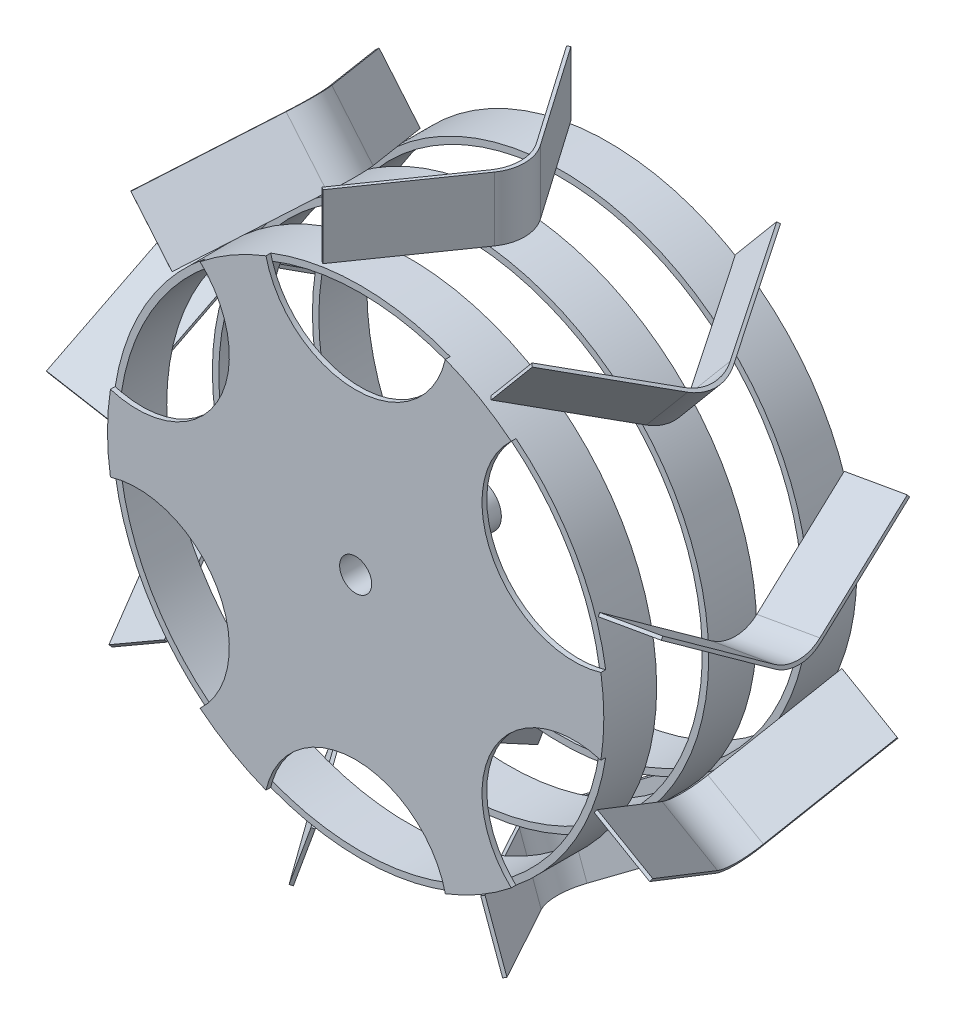
SolidWorks part; units mm, degrees
other "Папка сварных швов"
ref_plane "Спереди" through (0, 0, 0) normal (0, 0, 1) x (1, 0, 0)
ref_plane "Сверху" through (0, 0, 0) normal (0, 1, 0) x (1, 0, 0)
ref_plane "Справа" through (0, 0, 0) normal (1, 0, 0) x (0, 0, -1)
sketch "Эскиз1" plane through (0, 0, 0) normal (0, 0, 1) x (1, 0, 0)
  arc A0 (-56.0167, 144.5238) -> (-97.153, 120.7738) centre (0, 0) ccw
  arc A1 (-56.0167, 144.5238) -> (56.0167, 144.5238) centre (0, 157.5) ccw
  arc A2 (97.153, 120.7738) -> (153.1696, 23.75) centre (136.399, 78.75) ccw
  arc A3 (153.1696, -23.75) -> (97.153, -120.7738) centre (136.399, -78.75) ccw
  arc A4 (56.0167, -144.5238) -> (-56.0167, -144.5238) centre (0, -157.5) ccw
  arc A5 (-97.153, -120.7738) -> (-153.1696, -23.75) centre (-136.399, -78.75) ccw
  arc A6 (-153.1696, 23.75) -> (-97.153, 120.7738) centre (-136.399, 78.75) ccw
  arc A7 (97.153, 120.7738) -> (56.0167, 144.5238) centre (0, 0) ccw
  arc A8 (-153.1696, 23.75) -> (-153.1696, -23.75) centre (0, 0) ccw
  arc A9 (-97.153, -120.7738) -> (-56.0167, -144.5238) centre (0, 0) ccw
  arc A10 (56.0167, -144.5238) -> (97.153, -120.7738) centre (0, 0) ccw
  arc A11 (153.1696, -23.75) -> (153.1696, 23.75) centre (0, 0) ccw
  point P23 (0, 0)
  dimension "D1" = 310
  dimension "D2" = 115
  dimension "D3" = 100
  dimension "D4" = 6
extrude "Бобышка-Вытянуть1" add sketch "Эскиз1" against normal blind 3
sketch "Эскиз2" plane through (0, 0, -3) normal (0, 0, -1) x (-1, 0, 0)
  circle A0 centre (0, 0) radius 14
  circle A1 centre (0, 0) radius 10
  dimension "D1" = 28
  dimension "D2" = 20
extrude "Вырез-Вытянуть1" cut sketch "Эскиз2" against normal blind 3 contours A0
extrude "Бобышка-Вытянуть2" add sketch "Эскиз2<4>" along normal blind 74 and the other way blind 3
sketch "Эскиз2<4>" plane through (0, 0, -3) normal (0, 0, -1) x (-1, 0, 0) same geometry as "Эскиз2"
sketch "Эскиз4" plane through (0, 0, 0) normal (0, 1, 0) x (1, 0, 0)
  line L0 (14, 77) -> (-14, 77) construction
  circle A0 centre (0, 56.5) radius 4
  dimension "D1" = 8
  dimension "D2" = 16.5
extrude "Вырез-Вытянуть2" cut sketch "Эскиз4" against normal up to next and the other way up to next
sketch "Эскиз5" plane through (0, 0, -3) normal (0, 0, -1) x (-1, 0, 0)
  circle A0 centre (0, 0) radius 155
  circle A1 centre (0, 0) radius 151
  dimension "D1" = 310
  dimension "D2" = 4
extrude "Бобышка-Вытянуть3" add sketch "Эскиз5" along normal blind 30
ref_plane "Плоскость1" through (0, 0, -80.5) normal (0, 0, -1) x (-1, 0, 0)
ref_plane "Плоскость2" through (0, 0, -128) normal (0, 0, -1) x (-1, 0, 0)
sketch "Эскиз6" plane through (0, 0, -128) normal (0, 0, -1) x (-1, 0, 0)
  circle A0 centre (0, 0) radius 155
  circle A1 centre (0, 0) radius 151
  dimension "D1" = 310
  dimension "D2" = 4
sketch "Эскиз7" plane through (0, 0, -80.5) normal (0, 0, -1) x (-1, 0, 0)
  circle A0 centre (0, 0) radius 155
  circle A1 centre (0, 0) radius 151
  dimension "D1" = 310
  dimension "D2" = 4
extrude "Бобышка-Вытянуть4" add sketch "Эскиз7" along normal blind 15 and the other way blind 15 separate body
extrude "Бобышка-Вытянуть5" add sketch "Эскиз6" along normal blind 30 separate body
ref_plane "Плоскость3" through (0, 155, 0) normal (0, 1, 0) x (1, 0, 0)
sketch "Эскиз9" plane through (0, 155, 0) normal (0, 1, 0) x (1, 0, 0)
  line L0 (25, 80.5) -> (-25.1707, 80.5) construction
  line L1 (-25.1707, 4.1434) -> (-23.5298, 3)
  line L2 (-56.0167, 3) -> (56.0167, 3) construction
  line L6 (18.0742, 66.2079) -> (-25.1707, 4.1434)
  line L8 (20.5118, 66.2079) -> (-23.5298, 3)
  line L11 (0, 0) -> (0, 235.5945) construction
  line L12 (155, 80.5) -> (-183.1304, 80.5) construction
  line L13 (-25.1707, 156.8566) -> (-23.5298, 158)
  line L14 (-25.1707, 156.8566) -> (18.0742, 94.7921)
  line L15 (-23.5298, 158) -> (20.5118, 94.7921)
  arc A2 (20.5118, 94.7921) -> (20.5118, 66.2079) centre (0, 80.5) cw
  arc A3 (18.0742, 94.7921) -> (18.0742, 66.2079) centre (-2.4376, 80.5) cw
  point P35 (30.4702, 80.5)
  dimension "D3" = 54
  dimension "D1" = 25
  dimension "D2" = 25
  dimension "D4" = 2
  dimension "D5" = 2
extrude "Бобышка-Вытянуть6" add sketch "Эскиз9" along normal blind 40 separate body
pattern_circular "Круговой массив5" count 9 over 360 about axis through (0, 0, 0) along (0, 0, -1) of bodies 110
